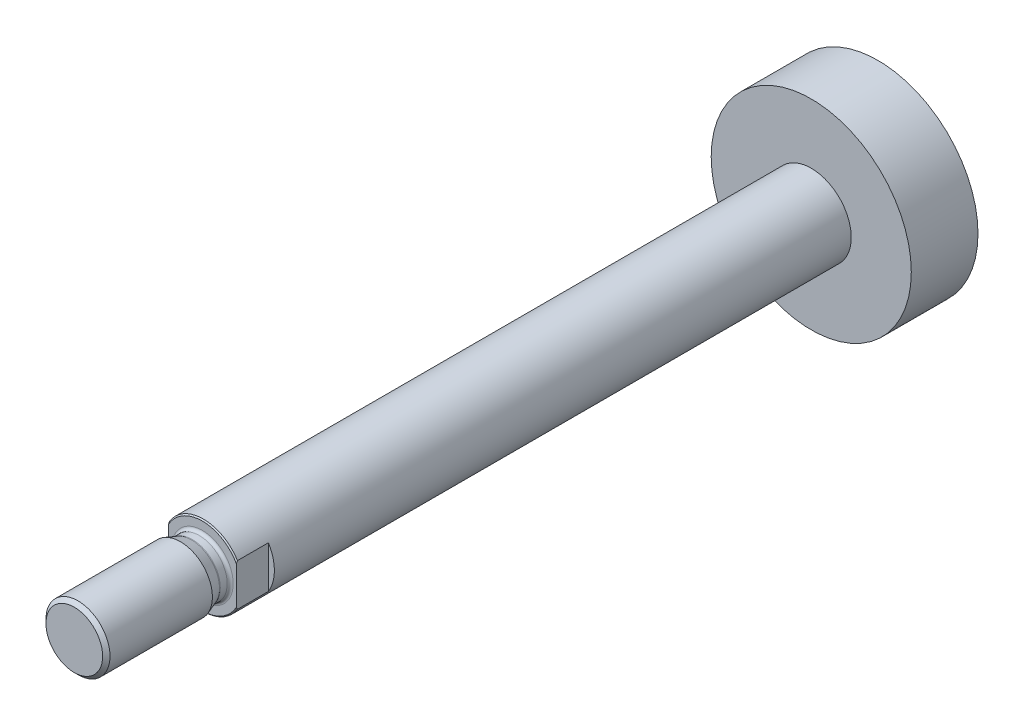
SolidWorks part; units mm, degrees
ref_plane "Front Plane" through (0, 0, 0) normal (0, 0, 1) x (1, 0, 0)
ref_plane "Top Plane" through (0, 0, 0) normal (0, 1, 0) x (1, 0, 0)
ref_plane "Right Plane" through (0, 0, 0) normal (1, 0, 0) x (0, 0, -1)
sketch "Sketch1" plane through (0, 0, 0) normal (1, 0, 0) x (0, 0, -1)
  line L0 (-35.8, 0) -> (-35.8, 9.7172)
  line L1 (-35.8, 9.7172) -> (-35.5172, 10)
  line L2 (-35.5172, 10) -> (116.3333, 10)
  line L3 (116.3333, 10) -> (116.3333, 25)
  line L4 (116.3333, 25) -> (133, 25)
  line L5 (133, 25) -> (133, 0)
  line L6 (133, 0) -> (-35.8, 0)
  line L7 (133, 0) -> (-35.8, 0) construction
revolve "Revolve1" add sketch "Sketch1" angle 360 about L7 reverse direction yes
ref_plane "Plane1" through (0, 0, -116.3333) normal (0, 0, 1) x (1, 0, 0)
sketch "Sketch2" plane through (0, 0, 0) normal (0, 1, 0) x (1, 0, 0)
  line L0 (-17, -61.8) -> (17, -61.8)
  line L1 (17, -61.8) -> (17, -27.8)
  line L2 (17, -27.8) -> (8.5, -27.8)
  line L3 (8.5, -27.8) -> (8.5, -43.8)
  line L4 (8.5, -43.8) -> (-8.5, -43.8)
  line L5 (-8.5, -43.8) -> (-8.5, -27.8)
  line L6 (-8.5, -27.8) -> (-17, -27.8)
  line L7 (-17, -27.8) -> (-17, -61.8)
extrude "Cut-Extrude1" cut sketch "Sketch2" along normal blind 17 and the other way blind 17
sketch "Sketch3" plane through (0, 0, 0) normal (1, 0, 0) x (0, 0, -1)
  line L0 (-67.8, 0) -> (-67.8, 7.08)
  line L1 (-67.8, 7.08) -> (-66.88, 8)
  line L2 (-66.88, 8) -> (-41.2849, 8)
  line L3 (-41.2849, 8) -> (-38.5243, 6.9952)
  line L4 (-38.2678, 6.95) -> (-36.55, 6.95)
  line L5 (-35.8, 7.7) -> (-35.05, 7.7)
  line L6 (-35.05, 7.7) -> (-35.05, 0)
  line L7 (-35.05, 0) -> (-67.8, 0)
  line L8 (-35.05, 0) -> (-67.8, 0) construction
  arc A0 (-38.5243, 6.9952) -> (-38.2678, 6.95) centre (-38.2678, 7.7) ccw
  arc A1 (-36.55, 6.95) -> (-35.8, 7.7) centre (-36.55, 7.7) ccw
revolve "Revolve2" add sketch "Sketch3" angle 360 about L8 reverse direction yes
cosmetic thread "Cosmetic Thread1" parameters "D1"=29.0428, "D2"=14.16
ref_plane "Plane2" through (0, 0, -133) normal (0, 0, 1) x (1, 0, 0)
ref_plane "Plane3" through (0, 0, 49.8) normal (0, 0, 1) x (1, 0, 0)
ref_plane "Plane4" through (0, 0, 49.8) normal (0, 0, 1) x (1, 0, 0)
ref_plane "FDT_PIRODACC XY" through (0, 0, 49.8) normal (0, 0, 1) x (1, 0, 0)
ref_plane "FDT_PIRODACC XZ" through (0, 0, 0) normal (0, -1, 0) x (-1, 0, 0)
ref_plane "FDT_PIRODACC YZ" through (0, 0, 0) normal (1, 0, 0) x (0, 0, -1)
ref_axis "FDT_PIRODACC X" through (-80.9, 0, 49.8) along (1, 0, 0)
ref_axis "FDT_PIRODACC Y" through (0, -50, 49.8) along (0, 1, 0)
ref_axis "FDT_PIRODACC Z" through (0, 0, 80.9) along (0, 0, -1)
sketch3d "FDT_PIRODACC"
  point P0 (0, 0, 49.8)
ref_plane "NUT XY" through (0, 0, 49.8) normal (0, 0, -1) x (-1, 0, 0)
ref_plane "NUT XZ" through (0, 0, 0) normal (0, 1, 0) x (1, 0, 0)
ref_plane "NUT YZ" through (0, 0, 0) normal (1, 0, 0) x (0, 0, -1)
ref_axis "NUT X" through (-80.9, 0, 49.8) along (1, 0, 0)
ref_axis "NUT Y" through (0, 50, 49.8) along (0, -1, 0)
ref_axis "NUT Z" through (0, 0, -80.9) along (0, 0, 1)
sketch3d "NUT"
  point P0 (0, 0, 49.8)
ref_plane "P XY" through (0, 0, -133) normal (0, 0, -1) x (-1, 0, 0)
ref_plane "P XZ" through (0, 0, 0) normal (-1, 0, 0) x (0, 0, 1)
ref_plane "P YZ" through (0, 0, 0) normal (0, 1, 0) x (1, 0, 0)
ref_axis "P X" through (0, -50, -133) along (0, 1, 0)
ref_axis "P Y" through (-80.9, 0, -133) along (1, 0, 0)
ref_axis "P Z" through (0, 0, -50) along (0, 0, 1)
sketch3d "P"
  point P0 (0, 0, -133)
